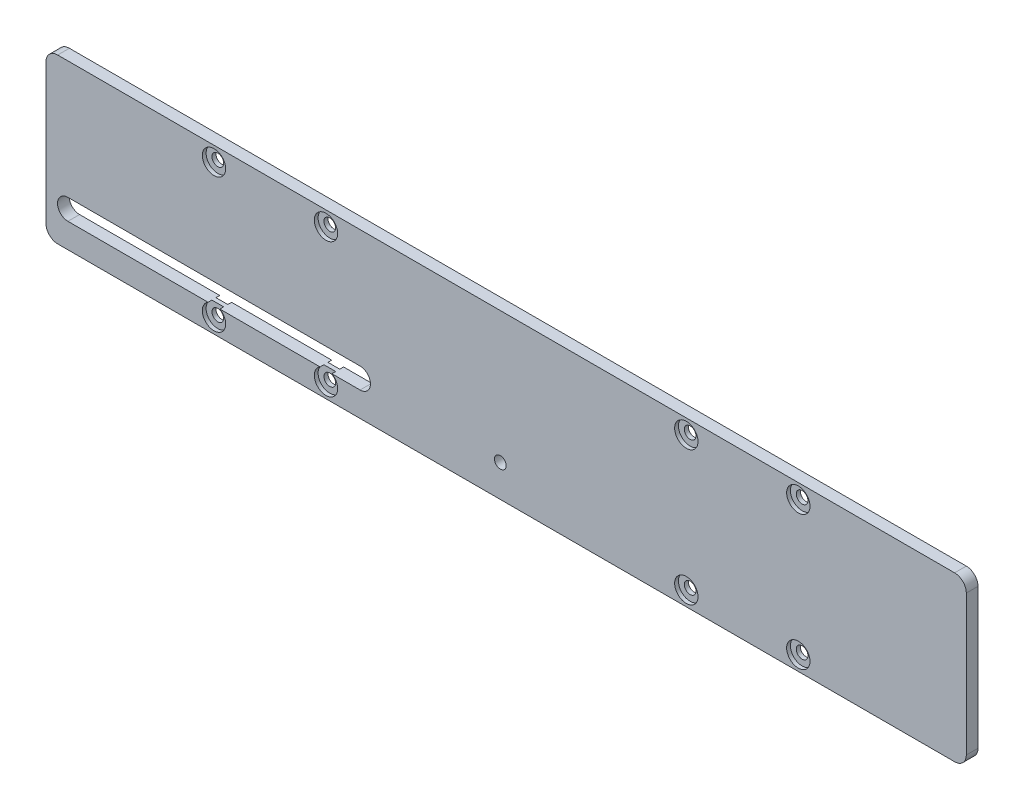
SolidWorks part; units mm, degrees
ref_plane "前视基准面" through (0, 0, 0) normal (0, 0, 1) x (1, 0, 0)
ref_plane "上视基准面" through (0, 0, 0) normal (0, 1, 0) x (1, 0, 0)
ref_plane "右视基准面" through (0, 0, 0) normal (1, 0, 0) x (0, 0, -1)
sketch "草图1" plane through (0, 0, 0) normal (0, 0, 1) x (1, 0, 0)
  line L0 (-150, -16) -> (-50, -16) construction
  line L1 (153.5, -28) -> (-153.5, -28)
  line L2 (157.5, -24) -> (157.5, 24)
  line L3 (153.5, 28) -> (-153.5, 28)
  line L4 (-157.5, -24) -> (-157.5, 24)
  line L5 (157.5, -28) -> (-157.5, 28) construction
  line L6 (157.5, 28) -> (-157.5, -28) construction
  line L7 (-150, -12.45) -> (-50, -12.45)
  line L8 (-150, -19.55) -> (-50, -19.55)
  line L9 (0, 28) -> (0, -28) construction
  arc A0 (157.5, -24) -> (153.5, -28) centre (153.5, -24) cw
  arc A1 (157.5, 24) -> (153.5, 28) centre (153.5, 24) ccw
  arc A2 (-157.5, -24) -> (-153.5, -28) centre (-153.5, -24) ccw
  arc A3 (-157.5, 24) -> (-153.5, 28) centre (-153.5, 24) cw
  arc A4 (-150, -12.45) -> (-150, -19.55) centre (-150, -16) ccw
  arc A5 (-50, -19.55) -> (-50, -12.45) centre (-50, -16) ccw
  circle A7 centre (-100, 23) radius 2
  circle A8 centre (-61.67, 23) radius 2
  circle A9 centre (-100, -23) radius 2
  circle A11 centre (-61.67, -23) radius 2
  circle A12 centre (100, -23) radius 2
  circle A13 centre (61.67, -23) radius 2
  circle A14 centre (61.67, 23) radius 2
  circle A15 centre (100, 23) radius 2
  point P0 (0, 0)
  point P20 (-100, -16)
  dimension "D3" = 4
  dimension "D5" = 7.5
  dimension "D6" = 3.55
  dimension "D7" = 46
  dimension "D8" = 5
  dimension "D9" = 12
  dimension "D10" = 4
  dimension "D11" = 4
  dimension "D12" = 4
  dimension "D13" = 4
  dimension "D14" = 38.33
  dimension "D15" = 38.33
  dimension "D16" = 46
  dimension "D17" = 5
  dimension "D18" = 5
  dimension "D19" = 100
  dimension "D20" = 12
  dimension "D1" = 315
  dimension "D2" = 56
  dimension "D4" = 100
extrude "凸台-拉伸1" add sketch "草图1" along normal blind 4
sketch "草图2" plane through (0, 0, 4) normal (0, 0, 1) x (1, 0, 0)
  line L0 (0, 28) -> (0, -28) construction
  line L1 (153.5, 28) -> (-153.5, 28) construction
  line L2 (-153.5, -28) -> (153.5, -28) construction
  circle A0 centre (-100, 23) radius 4
  circle A1 centre (-61.67, 23) radius 4
  circle A2 centre (-100, -23) radius 4
  circle A3 centre (-61.67, -23) radius 4
  circle A4 centre (61.67, -23) radius 4
  circle A5 centre (100, -23) radius 4
  circle A6 centre (61.67, 23) radius 4
  circle A7 centre (100, 23) radius 4
  dimension "D1" = 8
  dimension "D2" = 8
  dimension "D3" = 8
  dimension "D4" = 8
extrude "切除-拉伸1" cut sketch "草图2" against normal blind 1.3
sketch "草图3" plane through (0, 0, 4) normal (0, 0, 1) x (1, 0, 0)
  circle A2 centre (-2, -17) radius 2
extrude "切除-拉伸2" cut sketch "草图3" against normal blind 10
sketch "草图5" plane through (0, 0, 0) normal (0, 0, -1) x (-1, 0, 0)
  circle A0 centre (-100, -23) radius 4
  circle A1 centre (-61.67, -23) radius 4
  circle A2 centre (61.67, -23) radius 4
  circle A3 centre (100, -23) radius 4
  circle A4 centre (100, 23) radius 4
  circle A5 centre (61.67, 23) radius 4
  circle A6 centre (-61.67, 23) radius 4
  circle A7 centre (-100, 23) radius 4
extrude "切除-拉伸4" cut sketch "草图5" against normal blind 1.3
